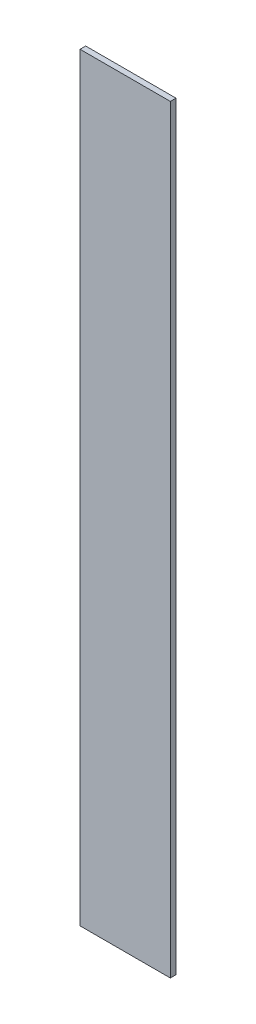
SolidWorks part; units mm, degrees
material "Acrylic (Medium-high impact)"
ref_plane "Front Plane" through (0, 0, 0) normal (0, 0, 1) x (1, 0, 0)
ref_plane "Top Plane" through (0, 0, 0) normal (0, 1, 0) x (1, 0, 0)
ref_plane "Right Plane" through (0, 0, 0) normal (1, 0, 0) x (0, 0, -1)
sketch "Sketch1" plane through (0, 0, 0) normal (0, 1, 0) x (1, 0, 0)
  line L0 (0, 0) -> (0, 76.2) construction
  line L2 (25.4, 68.667) -> (-25.4, 68.667)
  line L3 (25.4, 68.667) -> (25.4, 71.842)
  line L4 (25.4, 71.842) -> (-25.4, 71.842)
  line L5 (-25.4, 68.667) -> (-25.4, 71.842)
  line L6 (25.4, 68.667) -> (-25.4, 71.842) construction
  line L7 (25.4, 71.842) -> (-25.4, 68.667) construction
  circle A0 centre (0, 0) radius 76.2 construction
  point P4 (0, 70.2545)
  dimension "D1" = 152.4
  dimension "D2" = 3.175
  dimension "D3" = 50.8
extrude "Boss-Extrude1" add sketch "Sketch1" along normal blind 427.1518
sketch "Sketch2" plane through (0, 0, -68.667) normal (0, 0, 1) x (1, 0, 0)
  line L1 (-25.4, 427.1518) -> (25.4, 427.1518)
  line L2 (-25.4, 427.1518) -> (-25.4, 0)
  line L3 (-25.4, 0) -> (25.4, 0)
  line L4 (25.4, 427.1518) -> (25.4, 0)
